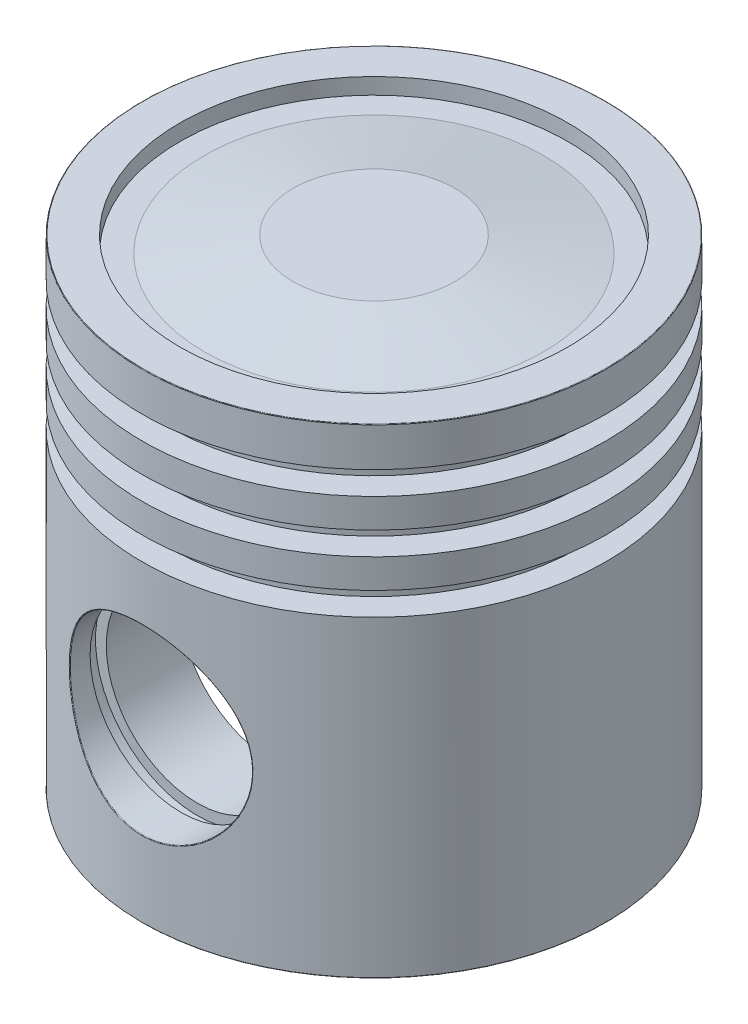
SolidWorks part; units mm, degrees
ref_plane "Alzado" through (0, 0, 0) normal (0, 0, 1) x (1, 0, 0)
ref_plane "Planta" through (0, 0, 0) normal (0, 1, 0) x (1, 0, 0)
ref_plane "Vista lateral" through (0, 0, 0) normal (1, 0, 0) x (0, 0, -1)
sketch "Croquis1" plane through (0, 0, 0) normal (0, 1, 0) x (1, 0, 0)
  circle A0 centre (0, 0) radius 43
  dimension "D1" = 86
extrude "Saliente-Extruir1" add sketch "Croquis1" along normal blind 89
sketch "Croquis3" plane through (0, 0, 0) normal (0, 0, 1) x (1, 0, 0)
  line L0 (43, 0) -> (43, 89) construction
  line L1 (38.3, 81.7) -> (47.7, 81.7)
  line L2 (38.3, 81.7) -> (38.3, 77.4)
  line L3 (38.3, 77.4) -> (47.7, 77.4)
  line L4 (47.7, 81.7) -> (47.7, 77.4)
  line L5 (38.3, 81.7) -> (47.7, 77.4) construction
  line L6 (38.3, 77.4) -> (47.7, 81.7) construction
  line L7 (43, 89) -> (-43, 89) construction
  line L8 (38.3, 72) -> (47.7, 72)
  line L9 (38.3, 72) -> (38.3, 67.7)
  line L10 (38.3, 67.7) -> (47.7, 67.7)
  line L11 (47.7, 72) -> (47.7, 67.7)
  line L12 (38.3, 72) -> (47.7, 67.7) construction
  line L13 (38.3, 67.7) -> (47.7, 72) construction
  line L14 (38.3, 62.3) -> (47.7, 62.3)
  line L15 (38.3, 62.3) -> (38.3, 58)
  line L16 (38.3, 58) -> (47.7, 58)
  line L17 (47.7, 62.3) -> (47.7, 58)
  line L18 (38.3, 62.3) -> (47.7, 58) construction
  line L19 (38.3, 58) -> (47.7, 62.3) construction
  line L20 (0, 0) -> (35.75, 0)
  line L21 (-43, 0) -> (43, 0) construction
  line L22 (35.75, 0) -> (35.75, 69.4098)
  line L23 (33.2153, 72.5399) -> (0, 79.6)
  line L24 (0, 79.6) -> (0, 0)
  line L25 (0, 79.6) -> (17.8345, 79.6) construction
  arc A0 (35.75, 69.4098) -> (33.2153, 72.5399) centre (32.55, 69.4098) ccw
  point P0 (43, 79.55)
  point P9 (38.3, 79.55)
  point P12 (43, 69.85)
  point P18 (43, 60.15)
  dimension "D11" = 6.4
  dimension "D1" = 4.3
  dimension "D2" = 38.3
  dimension "D3" = 7.3
  dimension "D4" = 4.3
  dimension "D5" = 4.3
  dimension "D6" = 5.4
  dimension "D7" = 5.4
  dimension "D8" = 35.75
  dimension "D9" = 2.1
  dimension "D10" = 12
revolve "Cortar-Revolución1" cut sketch "Croquis3" angle 360 about L24
sketch "Croquis4" plane through (0, 0, 0) normal (0, 0, 1) x (1, 0, 0)
  circle A0 centre (0, 31) radius 23.4
  circle A1 centre (0, 31) radius 16.9
  dimension "D1" = 46.8
  dimension "D3" = 33.8
  dimension "D2" = 31
extrude "Saliente-Extruir3" add sketch "Croquis4" along normal mid plane 71.5
sketch "Croquis5" plane through (0, 0, 0) normal (0, 0, 1) x (1, 0, 0)
  circle A1 centre (0, 31) radius 16.9
  circle A2 centre (0, 31) radius 16.9
  dimension "D1" = 0
extrude "Cortar-Extruir2" cut sketch "Croquis5" against normal mid plane 119
ref_plane "Plano1" through (0, -10, 0) normal (0, -1, 0) x (1, 0, 0)
sketch "Croquis6" plane through (0, -10, 0) normal (0, -1, 0) x (1, 0, 0)
  line L1 (-26.1102, 19) -> (26.1102, 19)
  line L2 (-26.1102, 19) -> (-26.1102, -19)
  line L3 (-26.1102, -19) -> (26.1102, -19)
  line L4 (26.1102, 19) -> (26.1102, -19)
  line L5 (-26.1102, 19) -> (26.1102, -19) construction
  line L6 (-26.1102, -19) -> (26.1102, 19) construction
  point P0 (0, 0)
  dimension "D1" = 38
extrude "Cortar-Extruir3" cut sketch "Croquis6" against normal blind 72
sketch "Croquis8" plane through (0, 0, 0) normal (0, -1, 0) x (1, 0, 0)
  circle A0 centre (0, 0) radius 39
  dimension "D1" = 78
extrude "Cortar-Extruir4" cut sketch "Croquis8" against normal blind 1 and the other way blind 5 from offset 5 offset against normal yes
sketch "Croquis10" plane through (0, 0, 0) normal (1, 0, 0) x (0, 0, -1)
  line L0 (-43, 14.1) -> (-43, 47.9) construction
  line L1 (-35.75, 49.9) -> (-32.75, 49.9)
  line L2 (-35.75, 49.9) -> (-35.75, 46.4817)
  line L3 (-35.75, 46.4817) -> (-32.75, 46.4817)
  line L4 (-32.75, 49.9) -> (-32.75, 46.4817)
  line L5 (-35.75, 15.1) -> (-32.75, 15.1)
  line L6 (-35.75, 15.1) -> (-35.75, 12.1)
  line L7 (-35.75, 12.1) -> (-32.75, 12.1)
  line L8 (-32.75, 15.1) -> (-32.75, 12.1)
  line L9 (-43, 31) -> (-22.4903, 31) construction
  dimension "D1" = 35.75
  dimension "D2" = 37.8
  dimension "D3" = 3
  dimension "D4" = 18.9
revolve "Cortar-Revolución2" cut sketch "Croquis10" angle 360 about L9 region at (0, 48.1909, 34.25)
mirror "Simetría1" about plane through (0, 0, 0) normal (0, 0, 1) of "Cortar-Revolución2"
sketch "Croquis11" plane through (0, 89, 0) normal (0, 1, 0) x (1, 0, 0)
  circle A0 centre (0, 0) radius 36
  dimension "D1" = 72
extrude "Cortar-Extruir5" cut sketch "Croquis11" against normal blind 3
sketch "Croquis12" plane through (0, 89, 0) normal (0, 1, 0) x (1, 0, 0)
  circle A0 centre (0, 0) radius 15
  dimension "D1" = 30
sketch "Croquis13" plane through (0, 86, 0) normal (0, 1, 0) x (1, 0, 0)
  line L0 (-31.5, 0) -> (-15, 0) construction
  circle A0 centre (0, 0) radius 31.5
  circle A1 centre (0, 0) radius 15 construction
  circle A2 centre (0, 0) radius 15 construction
  dimension "D1" = 63
loft "Recubrir1" add profiles "Croquis12", "Croquis13" connector at (-14.9722, 89, 0.912) connector at (-31.5, 86, 0)
fillet "Redondeo1" radius 0.1 4 edges at (2.4975, 14.2856, -42.9274) (-16.7094, 33.5312, 39.6207) (0, 0, 43) (0, 89, 43)
fillet "Redondeo2" radius 2 2 edges at (3.5909, 7.8772, 35.5692) (22.8289, 25.8617, -27.5119)
